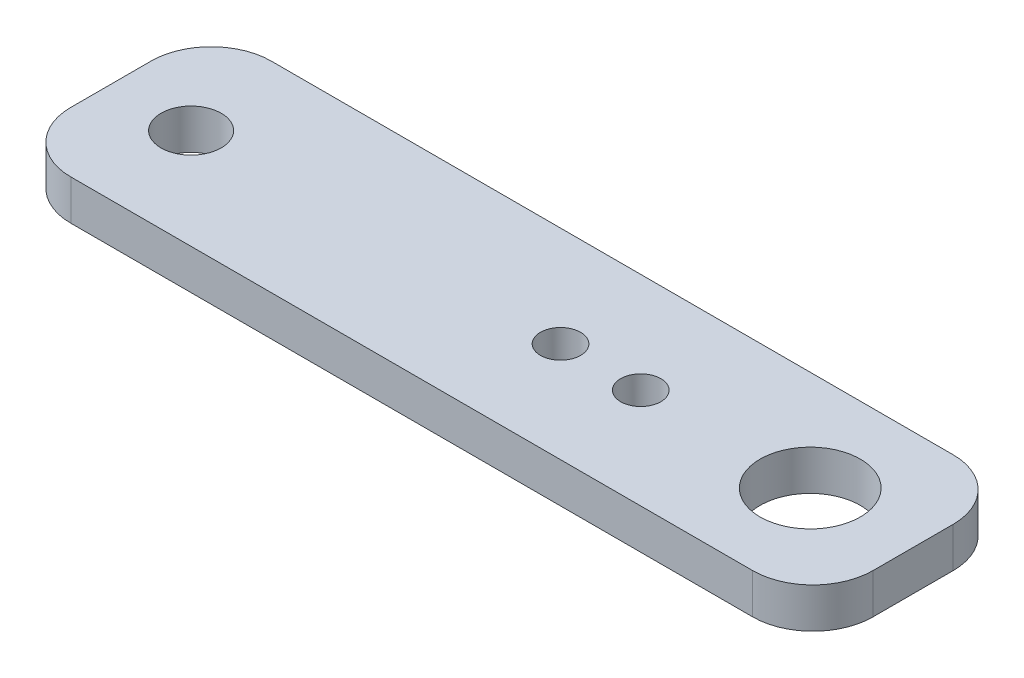
SolidWorks part; units mm, degrees
ref_plane "Front Plane" through (0, 0, 0) normal (0, 0, 1) x (1, 0, 0)
ref_plane "Top Plane" through (0, 0, 0) normal (0, 1, 0) x (1, 0, 0)
ref_plane "Right Plane" through (0, 0, 0) normal (1, 0, 0) x (0, 0, -1)
sketch "Sketch1" plane through (0, 0, 0) normal (0, 1, 0) x (1, 0, 0)
  line L1 (-20, 5) -> (20, 5)
  line L2 (-20, 5) -> (-20, -5)
  line L3 (-20, -5) -> (20, -5)
  line L4 (20, 5) -> (20, -5)
  line L5 (-20, 5) -> (20, -5) construction
  line L6 (-20, -5) -> (20, 5) construction
  point P0 (0, 0)
  dimension "D1" = 10
  dimension "D2" = 40
extrude "Boss-Extrude1" add sketch "Sketch1" along normal blind 2
hole_wizard "Ø5.0mm Dowel Hole1" positions "Sketch5" profile "Sketch6" hole size "Ø5.0" standard "ISO" end condition through all
sketch "Sketch5" plane through (0, 2, 0) normal (0, 1, 0) x (1, 0, 0)
  point P0 (14.8695, 0)
  point P9 (14.8695, 0)
sketch "Sketch6" plane through (14.8695, 2, 0) normal (1, 0, 0) x (0, 0, 1)
  line L0 (0, 0) -> (0, 2)
  line L1 (0, 2) -> (2.5, 2)
  line L2 (2.5, 2) -> (2.5, 0)
  line L5 (2.5, 0) -> (0, 0)
  line L11 (0, -6.35) -> (0, 107.95) construction
  dimension "Thru Hole Dia." = 5
  dimension "Thru Hole Depth" = 2
hole_wizard "Ø3.0mm Dowel Hole1" positions "Sketch3" profile "Sketch4" hole size "Ø3.0" standard "ISO" end condition through all
sketch "Sketch3" plane through (0, 2, 0) normal (0, 1, 0) x (1, 0, 0)
  line L0 (-20, 5) -> (-20, -5) construction
  point P0 (-16, 0)
  point P3 (-15.4747, 0)
  dimension "D1" = 4
sketch "Sketch4" plane through (-16, 2, 0) normal (1, 0, 0) x (0, 0, 1)
  line L0 (0, 0) -> (0, 2)
  line L1 (0, 2) -> (1.5, 2)
  line L2 (1.5, 2) -> (1.5, 0)
  line L5 (1.5, 0) -> (0, 0)
  line L11 (0, -6.35) -> (0, 107.95) construction
  dimension "Thru Hole Dia." = 3
  dimension "Thru Hole Depth" = 2
sketch "Sketch2" plane through (0, 2, 0) normal (0, 1, 0) x (1, 0, 0)
  line L0 (14.8695, 5) -> (14.8695, -5) construction
  line L1 (-20, -5) -> (20, -5) construction
  line L3 (20, 0) -> (-20, 0) construction
  line L4 (20, -5) -> (20, 5) construction
  line L5 (-20, 5) -> (-20, -5) construction
  circle A3 centre (6.4195, 0) radius 1
  circle A4 centre (2.4195, 0) radius 1
  point P10 (14.8695, 0)
  dimension "D1" = 2
  dimension "D2" = 8.45
  dimension "D3" = 4
extrude "Cut-Extrude1" cut sketch "Sketch2" against normal blind 3
fillet "Fillet1" radius 3 4 edges at (20, 1, 5) (20, 1, -5) (-20, 1, -5) (-20, 1, 5)
equation "\"globalength1\"=55"
